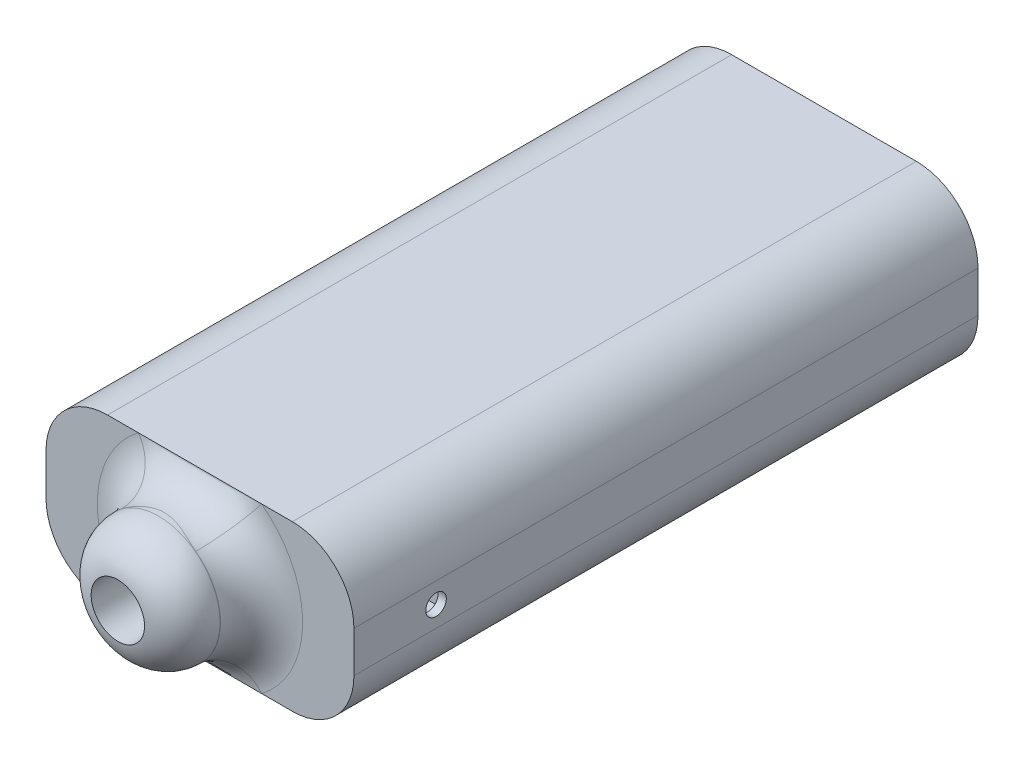
SolidWorks part; units mm, degrees
material "PLA Aero Bambu"
ref_plane "Front Plane" through (0, 0, 0) normal (0, 0, 1) x (1, 0, 0)
ref_plane "Top Plane" through (0, 0, 0) normal (0, 1, 0) x (1, 0, 0)
ref_plane "Right Plane" through (0, 0, 0) normal (1, 0, 0) x (0, 0, -1)
sketch "Sketch1" plane through (0, 0, 0) normal (0, 0, 1) x (1, 0, 0)
  line L1 (-18.75, 10) -> (18.75, 10)
  line L2 (-18.75, 10) -> (-18.75, -10)
  line L3 (-18.75, -10) -> (18.75, -10)
  line L4 (18.75, 10) -> (18.75, -10)
  line L5 (-18.75, 10) -> (18.75, -10) construction
  line L6 (-18.75, -10) -> (18.75, 10) construction
  circle A0 centre (0, 0) radius 2
  point P0 (0, 0)
  dimension "D3" = 4
  dimension "D1" = 20
  dimension "D2" = 37.5
extrude "Boss-Extrude1" add sketch "Sketch1" against normal blind 1
sketch "Sketch2" plane through (0, 0, -1) normal (0, 0, -1) x (-1, 0, 0)
  line L0 (-18.75, 10) -> (-18.75, -10)
  line L1 (18.75, -10) -> (-18.75, -10) construction
  line L2 (-18.75, -10) -> (18.75, -10)
  line L3 (18.75, -10) -> (18.75, 10)
  line L4 (18.75, 10) -> (-18.75, 10)
  line L5 (17.75, 9) -> (-17.75, 9)
  line L6 (-17.75, 9) -> (-17.75, -9)
  line L7 (-17.75, -9) -> (17.75, -9)
  line L8 (17.75, -9) -> (17.75, 9)
  dimension "D1" = 1
extrude "Boss-Extrude2" add sketch "Sketch2" along normal blind 75
fillet "Fillet2" radius 7.5 8 edges at (18.75, 10, -38) (18.75, -10, -38) (-18.75, -10, -38) (-18.75, 10, -38) (-17.75, -9, -38.5) (-17.75, 9, -38.5) (17.75, 9, -38.5) (17.75, -9, -38.5)
sketch "Sketch4" plane through (0, 0, 0) normal (0, 0, 1) x (1, 0, 0)
  circle A0 centre (0, 0) radius 7.5
  circle A1 centre (0, 0) radius 3.25
  dimension "D1" = 6.5
  dimension "D2" = 15
extrude "Boss-Extrude3" add sketch "Sketch4" along normal blind 10
fillet "Fillet3" radius 5 2 edges at (7.5, 0, 0) (7.5, 0, 10)
sketch "Sketch6" plane through (0, -9, 0) normal (0, 1, 0) x (1, 0, 0)
  line L0 (-11.25, 76) -> (-11.25, 0) construction
  line L1 (-11.25, 19) -> (11.25, 19)
  line L2 (-11.25, 19) -> (-11.25, 41.45)
  line L3 (-11.25, 41.45) -> (11.25, 41.45)
  line L4 (11.25, 19) -> (11.25, 41.45)
  line L5 (11.25, 0) -> (11.25, 76) construction
  line L9 (10.25, 1) -> (-10.25, 1) construction
  dimension "D1" = 18
  dimension "D2" = 22.45
extrude "Boss-Extrude4" add sketch "Sketch6" along normal blind 2.9
sketch "Sketch7" plane through (0, 9, 0) normal (0, -1, 0) x (1, 0, 0)
  line L0 (11.25, 0) -> (11.25, -76) construction
  line L1 (11.25, -19) -> (-11.25, -19)
  line L2 (11.25, -19) -> (11.25, -41.45)
  line L3 (11.25, -41.45) -> (-11.25, -41.45)
  line L4 (-11.25, -19) -> (-11.25, -41.45)
  line L5 (-11.25, -76) -> (-11.25, 0) construction
  line L6 (11.25, -41.45) -> (-11.25, -41.45) construction
  line L7 (-11.25, -19) -> (11.25, -19) construction
extrude "Boss-Extrude5" add sketch "Sketch7" along normal blind 3
sketch "Sketch8" plane through (-17.75, 0, 0) normal (1, 0, 0) x (0, 0, -1)
  line L0 (76, 1.5) -> (1, 1.5) construction
  line L1 (19, 1.5) -> (38.5, 1.5)
  line L2 (19, 1.5) -> (19, -1.5)
  line L3 (19, -1.5) -> (38.5, -1.5)
  line L4 (38.5, 1.5) -> (38.5, -1.5)
  line L5 (1, -1.5) -> (76, -1.5) construction
  line L6 (1, -1.5) -> (1, 1.5) construction
  dimension "D1" = 18
extrude "Boss-Extrude6" add sketch "Sketch8" along normal blind 2.5
sketch "Sketch9" plane through (0, 0, -1) normal (0, 0, -1) x (-1, 0, 0)
  line L0 (11.25, 6) -> (-11.25, 6) construction
  line L1 (-5.75, 4) -> (-3.25, 4)
  line L2 (-5.75, 4) -> (-5.75, -4.1)
  line L3 (-5.75, -4.1) -> (-3.25, -4.1)
  line L4 (-3.25, 4) -> (-3.25, -4.1)
  line L5 (-11.25, -6.1) -> (11.25, -6.1) construction
  line L6 (-17.75, 1.5) -> (-17.75, -1.5) construction
  dimension "D1" = 2
  dimension "D2" = 2
  dimension "D3" = 12
  dimension "D4" = 2.5
extrude "Boss-Extrude7" add sketch "Sketch9" along normal blind 6.5
sketch "Sketch5" plane through (18.75, 0, 0) normal (1, 0, 0) x (0, 0, -1)
  circle A0 centre (10, 0) radius 1.25
  dimension "D1" = 2.5
  dimension "D2" = 10
extrude "Cut-Extrude1" cut sketch "Sketch5" against normal through all
